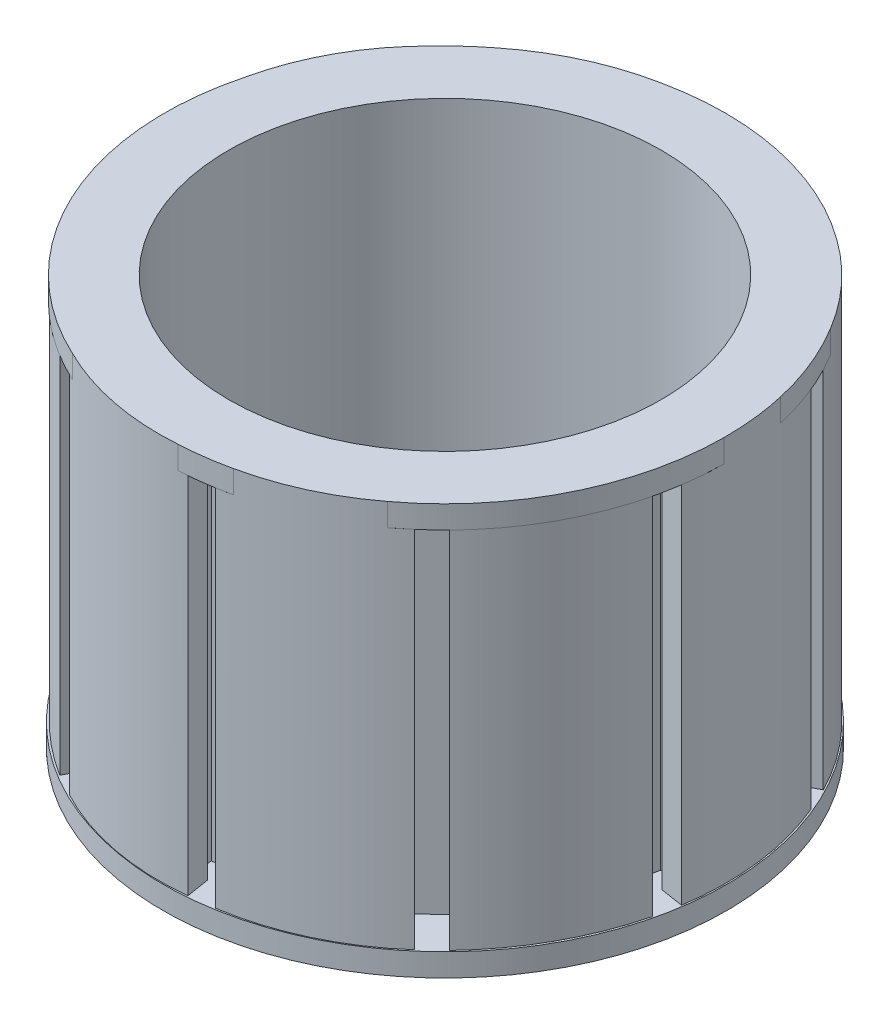
SolidWorks part; units mm, degrees
ref_plane "Alzado" through (0, 0, 0) normal (0, 0, 1) x (1, 0, 0)
ref_plane "Planta" through (0, 0, 0) normal (0, 1, 0) x (1, 0, 0)
ref_plane "Vista lateral" through (0, 0, 0) normal (1, 0, 0) x (0, 0, -1)
sketch "Sketch3" plane through (0, 0, 0) normal (1, 0, 0) x (0, 0, -1)
  line L0 (0, 0) -> (0, 36)
  dimension "D1" = 36
sketch "Sketch2" plane through (0, 0, 0) normal (0, 1, 0) x (1, 0, 0)
  circle A0 centre (0, 0) radius 24.5
sketch "Sketch1" plane through (0, 0, 0) normal (0, 1, 0) x (1, 0, 0)
  line L0 (0, 0) -> (-24.5, 0) construction
  line L1 (0, 0) -> (0, 24.5) construction
  line L2 (0, 0) -> (0, -24.5) construction
  line L3 (0, 0) -> (24.5, 0) construction
  line L4 (0, 0) -> (-24.179, 4.7253) construction
  line L5 (-17.5664, 3.433) -> (-17.9871, 1.2802) construction
  line L6 (-17.9871, 1.2802) -> (-20.8948, 1.8485) construction
  line L7 (-20.8948, 1.8485) -> (-20.6845, 2.9249) construction
  line L8 (-20.6845, 2.9249) -> (-24.2404, 3.557) construction
  line L9 (-17.9871, 1.2802) -> (-17.1533, 5.5802) construction
  line L10 (-20.0277, 6.1489) -> (-20.2564, 5.0738) construction
  line L11 (-20.0277, 6.1489) -> (-17.1459, 5.586) construction
  line L12 (-20.2564, 5.0738) -> (-23.8257, 5.7083) construction
  line L13 (-24.2404, 3.557) -> (-20.6845, 2.9249)
  line L14 (-20.6845, 2.9249) -> (-20.8948, 1.8485)
  line L15 (-20.8948, 1.8485) -> (-17.9871, 1.2802)
  line L16 (-17.9871, 1.2802) -> (-17.1533, 5.5802)
  line L17 (-17.1533, 5.5802) -> (-20.0277, 6.1489)
  line L18 (-20.0277, 6.1489) -> (-20.2564, 5.0738)
  line L19 (-20.2564, 5.0738) -> (-23.8257, 5.7083)
  line L20 (-20.2564, 5.0738) -> (-20.6845, 2.9249) construction
  circle A1 centre (0, 0) radius 24.5 construction
  arc A3 (-23.8257, 5.7083) -> (-24.2404, 3.557) centre (0, 0) cw
  dimension "D1" = 24.5
  dimension "D2" = 24.5
  dimension "D3" = 24.5
  dimension "D4" = 24.5
ref_plane "Plane4" through (0, 0, 0) normal (1, 0, 0) x (0, 0, -1)
sketch "Sketch5" plane through (0, 0, 0) normal (0, 1, 0) x (1, 0, 0)
  line L0 (0.0754, 0) -> (-24.4246, 0) construction
  line L1 (0.0754, 0) -> (0.0754, 24.5) construction
  line L2 (0.0754, 0) -> (0.0754, -24.5) construction
  line L3 (0.0754, 0) -> (24.5754, 0) construction
  line L4 (0.0754, 0) -> (-24.1036, 4.7253) construction
  line L5 (-17.5664, 3.433) -> (-20.7765, 1.8254) construction
  line L6 (-20.7765, 1.8254) -> (-22.5261, 2.1673) construction
  line L7 (-22.5261, 2.1673) -> (-22.3133, 3.2565) construction
  line L8 (-22.3133, 3.2565) -> (-24.363, 3.5724) construction
  line L9 (-20.7765, 1.8254) -> (-19.9414, 6.1319) construction
  line L10 (-21.677, 6.4753) -> (-21.8849, 5.4053) construction
  line L11 (-21.677, 6.4753) -> (-17.1459, 5.586) construction
  line L12 (-21.8849, 5.4053) -> (-23.9442, 5.7227) construction
  line L13 (-24.363, 3.5724) -> (-22.3133, 3.2565)
  line L14 (-22.3133, 3.2565) -> (-22.5261, 2.1673)
  line L15 (-22.5261, 2.1673) -> (-20.7765, 1.8254)
  line L16 (-20.7765, 1.8254) -> (-19.9414, 6.1319)
  line L17 (-19.9414, 6.1319) -> (-21.677, 6.4753)
  line L18 (-21.677, 6.4753) -> (-21.8849, 5.4053)
  line L19 (-21.8849, 5.4053) -> (-23.9442, 5.7227)
  line L20 (-21.8849, 5.4053) -> (-22.3133, 3.2565) construction
  line L21 (0, 0) -> (-24.5, 0) construction
  line L22 (-17.6103, 17.2103) -> (-16.1377, 15.7499)
  line L23 (-16.1377, 15.7499) -> (-16.9501, 14.9939)
  line L24 (-16.9501, 14.9939) -> (-15.7356, 13.6889)
  line L25 (-15.7356, 13.6889) -> (-12.5287, 16.6821)
  line L26 (-12.5287, 16.6821) -> (-13.731, 17.98)
  line L27 (-13.731, 17.98) -> (-14.5281, 17.2367)
  line L28 (-14.5281, 17.2367) -> (-16.0075, 18.7038)
  line L29 (-4.1311, 24.2745) -> (-3.7981, 22.2275)
  line L30 (-3.7981, 22.2275) -> (-4.8997, 22.0934)
  line L31 (-4.8997, 22.0934) -> (-4.6843, 20.3237)
  line L32 (-4.6843, 20.3237) -> (-0.3305, 20.8603)
  line L33 (-0.3305, 20.8603) -> (-0.5402, 22.6171)
  line L34 (-0.5402, 22.6171) -> (-1.622, 22.4842)
  line L35 (-1.622, 22.4842) -> (-1.9565, 24.5407)
  line L36 (10.9261, 22.0667) -> (9.9923, 20.2149)
  line L37 (9.9923, 20.2149) -> (9.0222, 20.7539)
  line L38 (9.0222, 20.7539) -> (8.1563, 19.1955)
  line L39 (8.1563, 19.1955) -> (11.994, 17.0706)
  line L40 (11.994, 17.0706) -> (12.8569, 18.6151)
  line L41 (12.8569, 18.6151) -> (11.9036, 19.1435)
  line L42 (11.9036, 19.1435) -> (12.8418, 21.0039)
  line L43 (21.8098, 11.4301) -> (19.9659, 10.4809)
  line L44 (19.9659, 10.4809) -> (19.4979, 11.4872)
  line L45 (19.4979, 11.4872) -> (17.8814, 10.7354)
  line L46 (17.8814, 10.7354) -> (19.7372, 6.7605)
  line L47 (19.7372, 6.7605) -> (21.3432, 7.5028)
  line L48 (21.3432, 7.5028) -> (20.8825, 8.4906)
  line L49 (20.8825, 8.4906) -> (22.735, 9.4443)
  line L50 (24.363, -3.5724) -> (22.3133, -3.2565)
  line L51 (22.3133, -3.2565) -> (22.5261, -2.1673)
  line L52 (22.5261, -2.1673) -> (20.7765, -1.8254)
  line L53 (20.7765, -1.8254) -> (19.9414, -6.1319)
  line L54 (19.9414, -6.1319) -> (21.677, -6.4753)
  line L55 (21.677, -6.4753) -> (21.8849, -5.4053)
  line L56 (21.8849, -5.4053) -> (23.9442, -5.7227)
  line L57 (17.6103, -17.2103) -> (16.1377, -15.7499)
  line L58 (16.1377, -15.7499) -> (16.9501, -14.9939)
  line L59 (16.9501, -14.9939) -> (15.7356, -13.6889)
  line L60 (15.7356, -13.6889) -> (12.5287, -16.6821)
  line L61 (12.5287, -16.6821) -> (13.731, -17.98)
  line L62 (13.731, -17.98) -> (14.5281, -17.2367)
  line L63 (14.5281, -17.2367) -> (16.0075, -18.7038)
  line L64 (4.1311, -24.2745) -> (3.7981, -22.2275)
  line L65 (3.7981, -22.2275) -> (4.8997, -22.0934)
  line L66 (4.8997, -22.0934) -> (4.6843, -20.3237)
  line L67 (4.6843, -20.3237) -> (0.3305, -20.8603)
  line L68 (0.3305, -20.8603) -> (0.5402, -22.6171)
  line L69 (0.5402, -22.6171) -> (1.622, -22.4842)
  line L70 (1.622, -22.4842) -> (1.9565, -24.5407)
  line L71 (-10.9261, -22.0667) -> (-9.9923, -20.2149)
  line L72 (-9.9923, -20.2149) -> (-9.0222, -20.7539)
  line L73 (-9.0222, -20.7539) -> (-8.1563, -19.1955)
  line L74 (-8.1563, -19.1955) -> (-11.994, -17.0706)
  line L75 (-11.994, -17.0706) -> (-12.8569, -18.6151)
  line L76 (-12.8569, -18.6151) -> (-11.9036, -19.1435)
  line L77 (-11.9036, -19.1435) -> (-12.8418, -21.0039)
  line L78 (-21.8098, -11.4301) -> (-19.9659, -10.4809)
  line L79 (-19.9659, -10.4809) -> (-19.4979, -11.4872)
  line L80 (-19.4979, -11.4872) -> (-17.8814, -10.7354)
  line L81 (-17.8814, -10.7354) -> (-19.7372, -6.7605)
  line L82 (-19.7372, -6.7605) -> (-21.3432, -7.5028)
  line L83 (-21.3432, -7.5028) -> (-20.8825, -8.4906)
  line L84 (-20.8825, -8.4906) -> (-22.735, -9.4443)
  arc A12 (-24.363, 3.5724) -> (-22.735, -9.4443) centre (-0.5159, -0.0552) ccw
  arc A13 (-21.8098, -11.4301) -> (-12.8418, -21.0039) centre (0.6864, 0.6556) ccw
  arc A14 (-10.9261, -22.0667) -> (1.9565, -24.5407) centre (-0.4657, -2.3758) ccw
  arc A15 (4.1311, -24.2745) -> (16.0075, -18.7038) centre (0.5253, -1.1418) ccw
  arc A19 (12.8418, 21.0039) -> (21.8098, 11.4301) centre (0.8003, 0.737) cw
  arc A20 (22.735, 9.4443) -> (24.363, -3.5724) centre (0.6279, 0.0692) cw
  arc A23 (17.6103, -17.2103) -> (23.9442, -5.7227) centre (-0.9852, 0.5326) ccw
  arc A24 (-1.9565, 24.5407) -> (10.9261, 22.0667) centre (-0.0263, -0.1859) cw
  arc A25 (-23.9442, 5.7227) -> (-17.6103, 17.2103) centre (-3.0155, 1.6732) cw
  arc A26 (-16.0075, 18.7038) -> (-4.1311, 24.2745) centre (-0.6941, 1.5015) cw
  point P96 (0, 0)
  point P101 (0, 0)
  point P102 (0, 0)
  dimension "D1" = 10
extrude "Boss-Extrude1" add sketch "Sketch5" along normal blind 36
sketch "Sketch6" plane through (0, 36, 0) normal (0, 1, 0) x (1, 0, 0)
  circle A1 centre (0, 0) radius 4
  dimension "D1" = 8
extrude "Cut-Extrude1" cut sketch "Sketch6" against normal through all
sketch "Sketch7" plane through (0, 36, 0) normal (0, 1, 0) x (1, 0, 0)
  circle A1 centre (0, 0) radius 19
  dimension "D1" = 38
extrude "Cut-Extrude2" cut sketch "Sketch7" against normal blind 28
sketch "Sketch8" plane through (0, 36, 0) normal (0, 1, 0) x (1, 0, 0)
  circle A0 centre (0, 0) radius 24.6403
  circle A1 centre (0, 0) radius 19
  dimension "D1" = 38
extrude "Boss-Extrude2" add sketch "Sketch8" against normal blind 2
sketch "Sketch9" plane through (0, 0, 0) normal (0, -1, 0) x (1, 0, 0)
  circle A0 centre (0, 0) radius 24.7655
  circle A1 centre (0, 0) radius 19
  dimension "D1" = 38
extrude "Boss-Extrude3" add sketch "Sketch9" against normal blind 2
